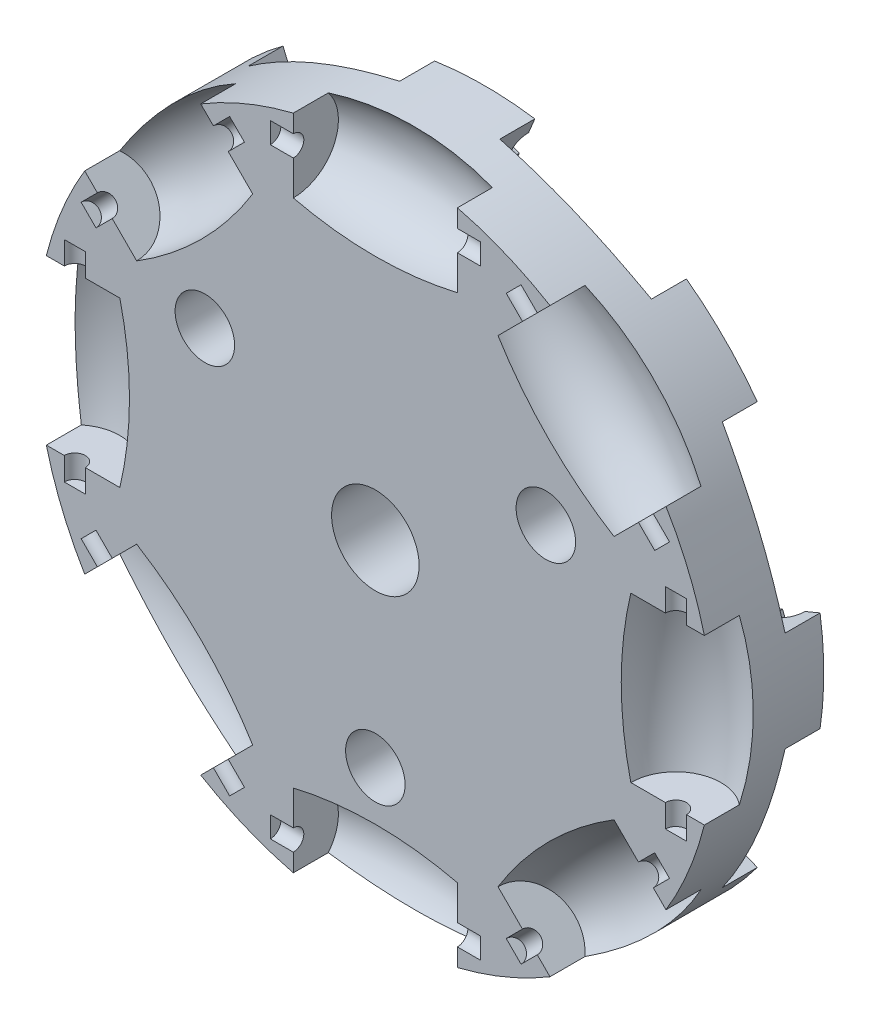
SolidWorks part; units mm, degrees
ref_plane "Front Plane" through (0, 0, 0) normal (0, 0, 1) x (1, 0, 0)
ref_plane "Top Plane" through (0, 0, 0) normal (0, 1, 0) x (1, 0, 0)
ref_plane "Right Plane" through (0, 0, 0) normal (1, 0, 0) x (0, 0, -1)
sketch "Sketch1" plane through (0, 0, 0) normal (0, 0, 1) x (1, 0, 0)
  circle A0 centre (0, 0) radius 24.6062
  point P11 (0, 0)
  dimension "D1" = 49.2125
extrude "Boss-Extrude1" add sketch "Sketch1" along normal mid plane 7.9375
ref_plane "Plane1" through (0, 0, 3.9688) normal (0, 0, 1) x (1, 0, 0)
ref_plane "Plane2" through (0, 0, -3.9688) normal (0, 0, 1) x (1, 0, 0)
sketch "Sketch5" plane through (0, 0, 3.9688) normal (0, 0, 1) x (1, 0, 0)
  line L0 (-5.9531, 25.0843) -> (-5.9531, 21.8122)
  line L1 (-5.9531, 21.8122) -> (5.9531, 21.8122)
  line L2 (5.9531, 21.8122) -> (5.9531, 25.0843)
  line L3 (-5.9531, 21.8122) -> (-8.0326, 21.8122) construction
  arc A2 (-5.9531, 25.0843) -> (5.9531, 25.0843) centre (0, 0) cw
  point P2 (0, 25.781)
  point P7 (0, 21.8122)
  dimension "D1" = 11.9062
  dimension "D2" = 7.9375
  dimension "D3" = 21.8122
revolve "Cut-Revolve5" cut sketch "Sketch5" angle 360 about L1
sketch "Sketch8" plane through (0, 0, -3.9688) normal (0, 0, 1) x (1, 0, 0)
  line L0 (4.0994, 25.453) -> (2.8472, 22.4301)
  line L1 (2.8472, 22.4301) -> (13.8472, 17.8737)
  line L2 (13.8472, 17.8737) -> (15.0993, 20.8967)
  line L3 (2.8472, 22.4301) -> (-2.3537, 24.5843) construction
  line L4 (0, 0) -> (9.4164, 22.7332) construction
  line L5 (0, 0) -> (0, 7.8748) construction
  arc A0 (4.0994, 25.453) -> (15.0993, 20.8967) centre (0, 0) cw
  arc A2 (-5.9531, 23.8753) -> (5.9531, 23.8753) centre (0, 0) ccw construction
  point P6 (8.3472, 20.1519)
  point P14 (9.866, 23.8185)
  dimension "D1" = 11.9062
  dimension "D2" = 7.9375
  dimension "D3" = 22.5
  dimension "D4" = 21.8122
revolve "Cut-Revolve6" cut sketch "Sketch8" angle 360 about L3
sketch "Sketch6" plane through (0, 0, 0) normal (1, 0, 0) x (0, 0, -1)
  arc A0 (-3.9688, 18.5402) -> (-1.429, 23.8753) centre (-3.9688, 21.8122) ccw construction
  circle A1 centre (-3.9688, 21.8122) radius 0.762
  point P4 (-3.9688, 21.8122)
  dimension "D1" = 1.524
extrude "Cut-Extrude2" cut sketch "Sketch6" against normal mid plane 15.24
ref_axis "Axis1" through (0, 0, -8.8615) along (0, 0, 1)
ref_plane "Plane3" through (0, 0, 0) normal (0.9239, -0.3827, 0) x (0, 0, -1)
sketch "Sketch10" plane through (0, 0, 0) normal (0.9239, -0.3827, 0) x (0, 0, -1)
  arc A1 (1.429, 23.8753) -> (3.9688, 18.5402) centre (3.9688, 21.8123) ccw construction
  circle A2 centre (3.9688, 21.8123) radius 0.889
  point P4 (3.9688, 21.8123)
  dimension "D1" = 1.778
extrude "Cut-Extrude3" cut sketch "Sketch10" against normal mid plane 15.875
pattern_circular "CirPattern1" count 8 over 360 about axis through (0, 0, 3.9688) along (0, 0, -1) of "Cut-Revolve5", "Cut-Revolve6", "Cut-Extrude2", "Cut-Extrude3"
sketch "Sketch16" plane through (0, 0, 3.9688) normal (0, 0, 1) x (1, 0, 0)
  circle A0 centre (0, -14.2875) radius 2.159
  circle A1 centre (-12.3733, 7.1437) radius 2.159
  circle A2 centre (12.3733, 7.1438) radius 2.159
  point P9 (0, 0)
  dimension "D1" = 4.318
  dimension "D2" = 14.2875
  dimension "D3" = 3
extrude "Cut-Extrude7" cut sketch "Sketch16" against normal through all
sketch "Sketch17" plane through (0, 0, 3.9688) normal (0, 0, 1) x (1, 0, 0)
  circle A0 centre (0, 0) radius 3.175
  dimension "D1" = 6.35
extrude "Cut-Extrude8" cut sketch "Sketch17" against normal through all
